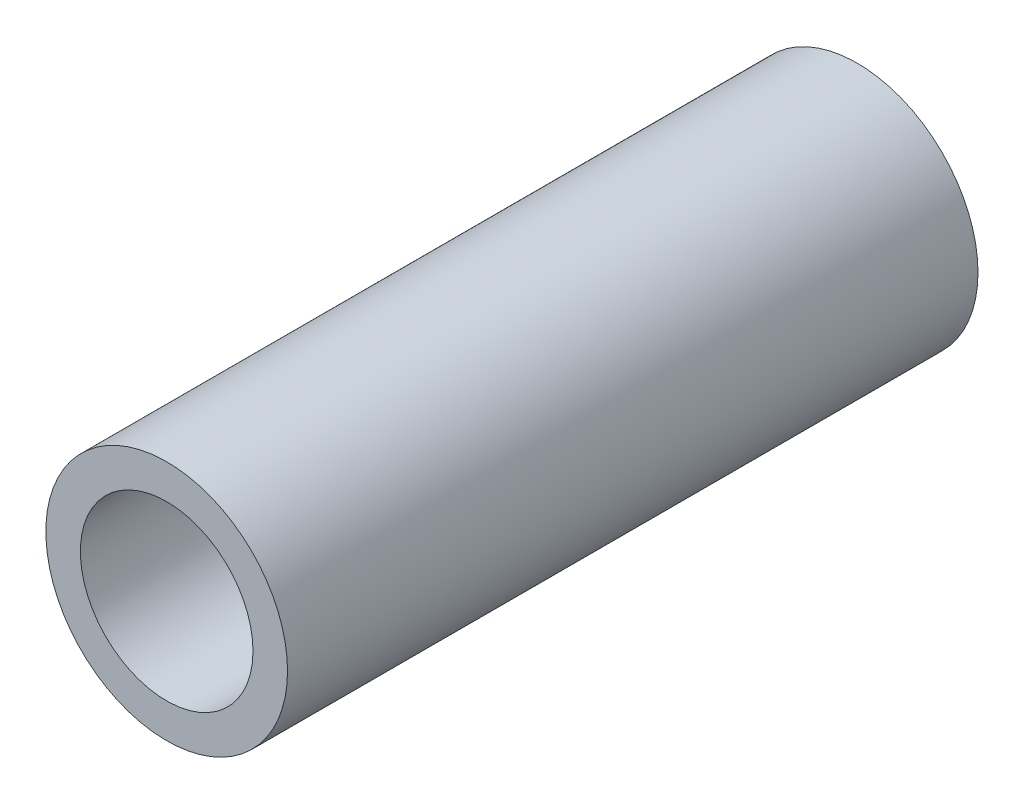
SolidWorks part; units mm, degrees
ref_plane "정면" through (0, 0, 0) normal (0, 0, 1) x (1, 0, 0)
ref_plane "윗면" through (0, 0, 0) normal (0, 1, 0) x (1, 0, 0)
ref_plane "우측면" through (0, 0, 0) normal (1, 0, 0) x (0, 0, -1)
ref_axis "기준축2" through (0, 0, 210) along (0, 0, -1)
ref_axis "기준축4" through (0, 55, 0) along (0, -1, 0)
sketch "스케치1" plane through (0, 0, 0) normal (0, 0, 1) x (1, 0, 0)
  circle A0 centre (0, 0) radius 35
  circle A1 centre (0, 0) radius 25
  dimension "D1" = 70
  dimension "D2" = 10
extrude "보스-돌출1" add sketch "스케치1" along normal blind 200
